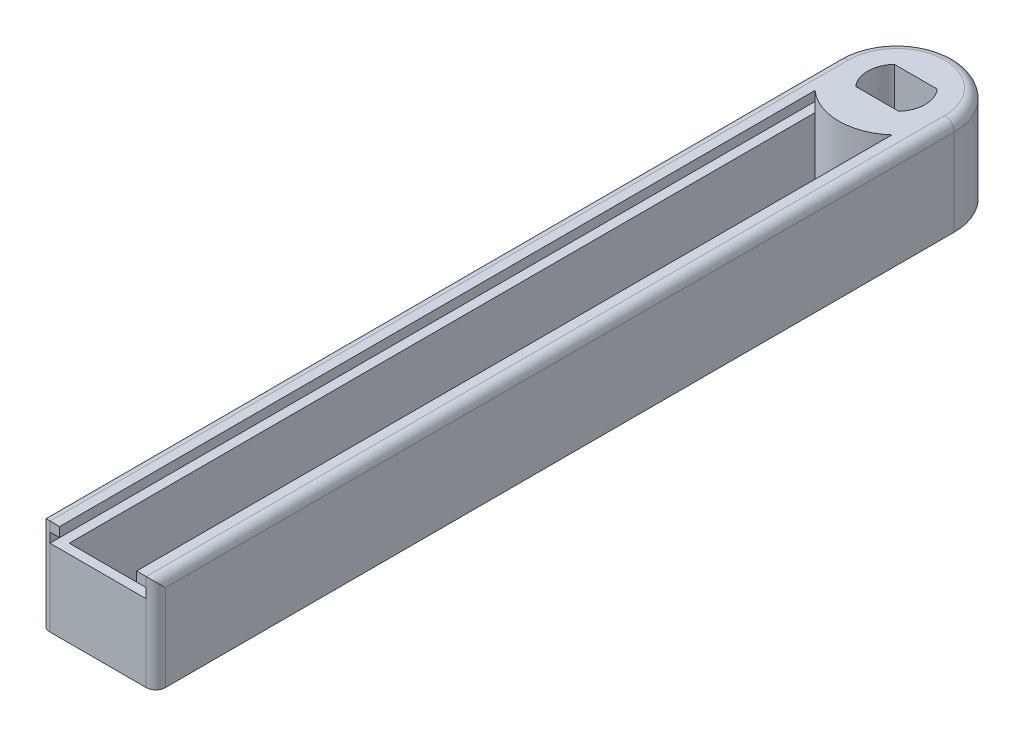
SolidWorks part; units mm, degrees
ref_plane "Front Plane" through (0, 0, 0) normal (0, 0, 1) x (1, 0, 0)
ref_plane "Top Plane" through (0, 0, 0) normal (0, 1, 0) x (1, 0, 0)
ref_plane "Right Plane" through (0, 0, 0) normal (1, 0, 0) x (0, 0, -1)
sketch "Sketch1" plane through (0, 0, 0) normal (0, 1, 0) x (1, 0, 0)
  line L0 (-3.3818, 6.9455) -> (-3.3818, -76.0545)
  line L1 (-9.3818, 6.9455) -> (2.6182, 6.9455)
  line L2 (-9.3818, 6.9455) -> (-9.3818, -76.0545)
  line L3 (-9.3818, -76.0545) -> (2.6182, -76.0545)
  line L4 (2.6182, 6.9455) -> (2.6182, -76.0545)
  line L5 (-8.3818, -76.0545) -> (-9.3818, -76.0545)
  line L6 (-8.3818, -76.0545) -> (-8.3818, 3.6288)
  line L7 (1.6182, -76.0545) -> (1.6182, 3.6288)
  line L8 (-9.3818, -75.0545) -> (2.6182, -75.0545)
  circle A0 centre (-3.3818, 6.9455) radius 6
  circle A1 centre (-3.3818, 6.9455) radius 2.5
  dimension "D3" = 1
  dimension "D1" = 12
  dimension "D2" = 83
extrude "Boss-Extrude2" add sketch "Sketch1" along normal blind 10 contours L1 A1 | L1 A1 L0 | L0 A1 L1 | A1 L0 A0 L1 | A1 L1 A0 L0 | A1 L1 A0 | A0 L7 L8 L4 | A0 L2 L8 L6 | L8 L2 L3 L6 | L8 L6 L3 L0 | L8 L0 L3 L7 | L8 L7 L3 L4
sketch "Sketch3" plane through (0, 10, 0) normal (0, 1, 0) x (1, 0, 0)
  line L4 (-5.8818, 8.4455) -> (-0.8818, 8.4455)
  line L5 (-5.8818, 8.4455) -> (-5.8818, 5.4455)
  line L6 (-5.8818, 5.4455) -> (-0.8818, 5.4455)
  line L7 (-0.8818, 8.4455) -> (-0.8818, 5.4455)
  line L8 (-5.8818, 8.4455) -> (-0.8818, 5.4455) construction
  line L9 (-5.8818, 5.4455) -> (-0.8818, 8.4455) construction
  circle A0 centre (-3.3818, 6.9455) radius 2.5
  dimension "D1" = 1.5
  dimension "D2" = 2.5
extrude "Cut-Extrude1" cut sketch "Sketch3" against normal blind 7.5 contours L6 A0 L4
sketch "Sketch4" plane through (0, 0, 0) normal (0, -1, 0) x (1, 0, 0)
  line L0 (-3.3818, -0.9455) -> (-3.3818, -12.9455)
  arc A0 (1.6182, -3.6288) -> (-8.3818, -3.6288) centre (-3.3818, -6.9455) ccw construction
  arc A1 (-9.3818, -6.9455) -> (2.6182, -6.9455) centre (-3.3818, -6.9455) ccw construction
  circle A2 centre (-3.3818, -6.9455) radius 2.5
extrude "Cut-Extrude2" cut sketch "Sketch4" against normal blind 2.5 contours L0 A2 | L0 A2
sketch "Sketch5" plane through (0, 0, 76.0545) normal (0, 0, 1) x (1, 0, 0)
  line L0 (-3.3818, 10) -> (-3.3818, 0)
  line L1 (-9.3818, 10) -> (2.6182, 10) construction
  line L3 (-8.3818, 9) -> (1.6182, 9)
  line L4 (-8.3818, 9) -> (-8.3818, 8)
  line L5 (-8.3818, 8) -> (1.6182, 8)
  line L6 (1.6182, 9) -> (1.6182, 8)
  line L7 (-9.3818, 0) -> (2.6182, 0) construction
  line L8 (-9.3818, 10) -> (-9.3818, 0) construction
  line L9 (2.6182, 10) -> (2.6182, 0) construction
  dimension "D1" = 1
  dimension "D2" = 1
  dimension "D3" = 1
  dimension "D4" = 1
extrude "Cut-Extrude3" cut sketch "Sketch5" against normal up to next contours L4 L5 L0 L3 | L6 L3 L0 L5
sketch "Sketch6" plane through (0, 0, 76.0545) normal (0, 0, 1) x (1, 0, 0)
  line L0 (-9.3818, 10) -> (2.6182, 10) construction
  line L1 (-8.3818, 9) -> (-6.3818, 9)
  line L2 (-8.3818, 9) -> (-8.3818, 10)
  line L3 (-8.3818, 10) -> (-6.3818, 10)
  line L4 (-6.3818, 9) -> (-6.3818, 10)
  line L5 (-3.3818, 10) -> (-3.3818, 0)
  line L6 (-9.3818, 0) -> (2.6182, 0) construction
  line L7 (1.6182, 7) -> (-0.3818, 7)
  line L8 (-8.3818, 8) -> (-6.3818, 8)
  line L9 (-8.3818, 8) -> (-8.3818, 7)
  line L10 (-8.3818, 7) -> (-6.3818, 7)
  line L11 (-6.3818, 8) -> (-6.3818, 7)
  line L12 (-0.3818, 8) -> (-0.3818, 7)
  line L13 (1.6182, 8) -> (-0.3818, 8)
  line L14 (1.6182, 8) -> (1.6182, 7)
  line L15 (1.6182, 10) -> (-0.3818, 10)
  line L16 (-0.3818, 9) -> (-0.3818, 10)
  line L17 (1.6182, 9) -> (-0.3818, 9)
  line L18 (1.6182, 9) -> (1.6182, 10)
  point P7 (-8.3818, 9.5)
  line M10 (1.6182, 8) -> (-8.3818, 8)
  line M12 (-8.3818, 9) -> (1.6182, 9)
  line M16 (2.6182, 10) -> (-9.3818, 10)
  dimension "D1" = 2
  dimension "1" = 1
extrude "Boss-Extrude3" add sketch "Sketch6" against normal blind 79.5 contours L4 L2 M12 M16 | L11 L9 L10 M10 | L14 L12 L7 M10 | L18 L16 M12 M16
fillet "Fillet1" radius 1 5 edges at (-9.3818, 10, 34.5545) (-3.3818, 10, -12.9455) (2.6182, 10, 34.5545) (-9.3818, 5, 76.0545) (2.6182, 5, 76.0545)
sketch "Sketch7" plane through (0, 0, 76.0545) normal (0, 0, 1) x (1, 0, 0)
  line L0 (-8.3818, 10) -> (1.6182, 10) construction
  line L1 (-7.3818, 10) -> (-6.3818, 10)
  line L2 (-7.3818, 10) -> (-7.3818, 9)
  line L3 (-7.3818, 9) -> (-6.3818, 9)
  line L4 (-6.3818, 10) -> (-6.3818, 9)
  line L5 (-8.2552, 9) -> (-6.3818, 9) construction
  line L6 (-8.3818, 10) -> (-8.3818, 9) construction
  line L7 (-3.3818, 10) -> (-3.3818, 9)
  line L8 (-8.3818, 9) -> (1.6182, 9) construction
  line L9 (0.6182, 9) -> (-0.3818, 9)
  line L10 (-0.3818, 10) -> (-0.3818, 9)
  line L11 (0.6182, 10) -> (-0.3818, 10)
  line L12 (0.6182, 10) -> (0.6182, 9)
  dimension "D1" = 1
  dimension "D2" = 1
extrude "Cut-Extrude7" cut sketch "Sketch7" against normal blind 79 contours L4 L1 L2 L7 | L12 L1 L10 L7
sketch "Sketch8" plane through (0, 10, 0) normal (0, 1, 0) x (1, 0, 0)
  line L0 (-5.3818, 8.4455) -> (-1.3818, 8.4455)
  line L1 (-5.3818, 5.4455) -> (-1.3818, 5.4455)
  circle A1 centre (-3.3818, 6.9455) radius 6
  circle A2 centre (-3.3818, 6.9455) radius 2.5
  line M3 (-1.3818, 5.4455) -> (-5.3818, 5.4455)
  arc M4 (-5.3818, 5.4455) -> (-5.3818, 8.4455) centre (-3.3818, 6.9455) cw
  line M5 (-5.3818, 8.4455) -> (-1.3818, 8.4455)
  arc M6 (-1.3818, 8.4455) -> (-1.3818, 5.4455) centre (-3.3818, 6.9455) cw
  line M7 (-7.3818, 2.9455) -> (-6.3818, 2.9455)
  line M8 (-6.3818, 2.9455) -> (-6.3818, 1.7493)
  arc M9 (-6.3818, 1.7493) -> (-0.3818, 1.7493) centre (-3.3818, 6.9455) ccw
  line M10 (-0.3818, 1.7493) -> (-0.3818, 2.9455)
  line M11 (-0.3818, 2.9455) -> (0.6182, 2.9455)
  line M12 (0.6182, 2.9455) -> (0.6182, -76.0545)
  arc M16 (1.4916, 3.4455) -> (1.6182, 3.6288) centre (-3.3818, 6.9455) ccw
  line M17 (1.6182, 3.6288) -> (1.6182, 6.9455)
  arc M18 (1.6182, 6.9455) -> (-8.3818, 6.9455) centre (-3.3818, 6.9455) ccw
  line M19 (-8.3818, 6.9455) -> (-8.3818, 3.6288)
  arc M20 (-8.3818, 3.6288) -> (-8.2552, 3.4455) centre (-3.3818, 6.9455) ccw
  line M24 (-7.3818, -76.0545) -> (-7.3818, 2.9455)
extrude "Boss-Extrude4" add sketch "Sketch8" against normal blind 3 contours A1 A2 M12 M16 M17 M18 M19 M20 M24 M7 M8 M9 M10 M11 M6 M4 | A1 M10 M12 M11 | A1 M24 M8 M7 | A2 M5 | A2 M3
sketch "Sketch9" plane through (-6.3818, 0, 0) normal (-1, 0, 0) x (0, 0, 1)
  line L1 (75.0545, 10) -> (76.0545, 10)
  line L2 (75.0545, 10) -> (75.0545, 9)
  line L3 (75.0545, 9) -> (76.0545, 9)
  line L4 (76.0545, 10) -> (76.0545, 9)
extrude "Cut-Extrude8" cut sketch "Sketch9" against normal blind 6
sketch "Sketch11" plane through (0, 0, 76.0545) normal (0, 0, 1) x (1, 0, 0)
  line L1 (-8.3818, 10) -> (-7.3818, 10)
  line L2 (-8.3818, 10) -> (-8.3818, 9)
  line L3 (-8.3818, 9) -> (-7.3818, 9)
  line L4 (-7.3818, 10) -> (-7.3818, 9)
extrude "Boss-Extrude5" add sketch "Sketch11" against normal blind 80
sketch "Sketch12" plane through (0, 0, 76.0545) normal (0, 0, 1) x (1, 0, 0)
  line L1 (0.6182, 10) -> (1.6182, 10)
  line L2 (0.6182, 10) -> (0.6182, 9)
  line L3 (0.6182, 9) -> (1.6182, 9)
  line L4 (1.6182, 10) -> (1.6182, 9)
extrude "Boss-Extrude6" add sketch "Sketch12" against normal blind 80
sketch "Sketch13" plane through (0, 8, 0) normal (0, 1, 0) x (1, 0, 0)
  line L0 (-3.3818, -75.0545) -> (-3.3818, -76.0545)
  line L1 (-8.3818, -76.0545) -> (-7.3818, -76.0545)
  line L2 (-8.3818, -76.0545) -> (-8.3818, 3.5534)
  line L3 (-8.3818, 3.5534) -> (-7.3818, 3.5534)
  line L4 (-7.3818, -76.0545) -> (-7.3818, 3.5534)
  line L5 (-6.3818, -75.0545) -> (-0.3818, -75.0545) construction
  line L6 (-8.3818, -76.0545) -> (1.6182, -76.0545) construction
  line L7 (1.6182, 3.5534) -> (0.6182, 3.5534)
  line L8 (0.6182, -76.0545) -> (0.6182, 3.5534)
  line L9 (1.6182, -76.0545) -> (0.6182, -76.0545)
  line L10 (1.6182, -76.0545) -> (1.6182, 3.5534)
  line M6 (-8.3818, -76.0545) -> (1.6182, -76.0545)
  line M7 (1.6182, -76.0545) -> (1.6182, 3.4455)
  line M8 (1.6182, 3.4455) -> (1.4916, 3.4455)
  arc M9 (1.4916, 3.4455) -> (-0.3818, 1.7493) centre (-3.3818, 6.9455) cw
  arc M13 (-6.3818, 1.7493) -> (-8.2552, 3.4455) centre (-3.3818, 6.9455) cw
  line M14 (-8.2552, 3.4455) -> (-8.3818, 3.4455)
  line M15 (-8.3818, 3.4455) -> (-8.3818, -76.0545)
  dimension "D1" = 79.608
  dimension "D2" = 1
extrude "Boss-Extrude7" add sketch "Sketch13" against normal blind 8 contours L4 M6 M13 M14 M15 | L8 M6 M7 M8 M9
sketch "Sketch14" plane through (0, 8, 0) normal (0, 1, 0) x (1, 0, 0)
  line L0 (-7.3818, 2.4733) -> (-7.3818, -75.0545)
  line L1 (-7.3818, 2.4733) -> (-7.3818, -76.0545) construction
  line L2 (-7.3818, -75.0545) -> (0.6182, -75.0545)
  line L3 (0.6182, 2.4733) -> (0.6182, -76.0545) construction
  line L4 (0.6182, -75.0545) -> (0.6182, 2.4733)
  circle A0 centre (-3.3818, 6.9455) radius 6
  arc M2 (1.4916, 3.4455) -> (-0.3818, 1.7493) centre (-3.3818, 6.9455) cw
  line M3 (-0.3818, 1.7493) -> (-0.3818, -75.0545)
  line M5 (-6.3818, -75.0545) -> (-6.3818, 1.7493)
  arc M6 (-6.3818, 1.7493) -> (-8.2552, 3.4455) centre (-3.3818, 6.9455) cw
extrude "Cut-Extrude9" cut sketch "Sketch14" against normal blind 1 contours L2 L4 M2 M3 | L0 L2 M5 M6
sketch "Sketch15" plane through (0, 0, 0) normal (0, -1, 0) x (1, 0, 0)
  circle A0 centre (-3.3818, -6.9455) radius 3
extrude "Cut-Extrude10" cut sketch "Sketch15" against normal up to vertex (2.5 mm away)
sketch "Sketch16" plane through (0, 2.5, 0) normal (0, -1, 0) x (1, 0, 0)
  point P0 (-3.3818, -6.9455)
sketch "Sketch17" plane through (0, 10, 0) normal (0, 1, 0) x (1, 0, 0)
  line L4 (-6.8818, 8.9455) -> (0.1182, 8.9455)
  line L5 (-6.8818, 8.9455) -> (-6.8818, 4.9455)
  line L6 (-6.8818, 4.9455) -> (0.1182, 4.9455)
  line L7 (0.1182, 8.9455) -> (0.1182, 4.9455)
  line L8 (-6.8818, 8.9455) -> (0.1182, 4.9455) construction
  line L9 (-6.8818, 4.9455) -> (0.1182, 8.9455) construction
  circle A0 centre (-3.3818, 6.8269) radius 0.0248
  circle A1 centre (-3.3818, 6.9455) radius 3
  point P3 (-3.3818, 6.9455)
  line M13 (-1.3818, 5.4455) -> (-5.3818, 5.4455)
  arc M14 (-5.3818, 5.4455) -> (-5.3818, 8.4455) centre (-3.3818, 6.9455) cw
  line M15 (-5.3818, 8.4455) -> (-1.3818, 8.4455)
  arc M16 (-1.3818, 8.4455) -> (-1.3818, 5.4455) centre (-3.3818, 6.9455) cw
extrude "Cut-Extrude13" cut sketch "Sketch17" against normal up to next contours L6 A1 L4 M16 M13 M14 M15
